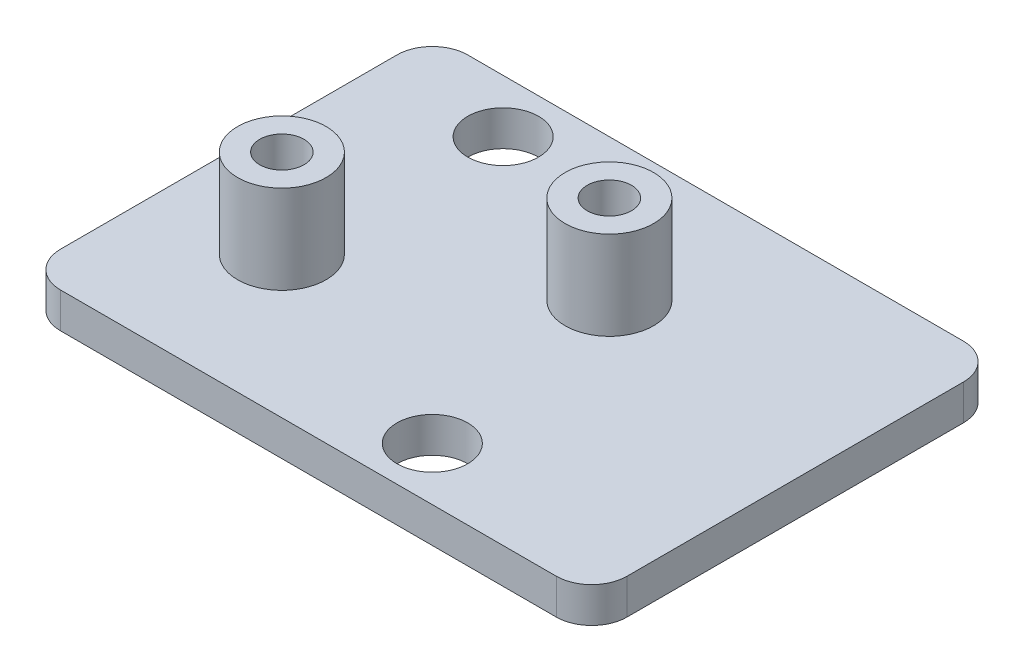
SolidWorks part; units mm, degrees
material "ABS"
ref_plane "Спереди" through (0, 0, 0) normal (0, 0, 1) x (1, 0, 0)
ref_plane "Сверху" through (0, 0, 0) normal (0, 1, 0) x (1, 0, 0)
ref_plane "Справа" through (0, 0, 0) normal (1, 0, 0) x (0, 0, -1)
sketch "Эскиз1" plane through (0, 0, 0) normal (0, 1, 0) x (1, 0, 0)
  line L1 (0, 0) -> (32, 0)
  line L2 (0, 0) -> (0, -23)
  line L3 (0, -23) -> (32, -23)
  line L4 (32, 0) -> (32, -23)
  dimension "D1" = 32
  dimension "D2" = 23
extrude "Бобышка-Вытянуть1" add sketch "Эскиз1" along normal blind 2
sketch "Эскиз4" plane through (0, 2, 0) normal (0, 1, 0) x (1, 0, 0)
  line L0 (0, 0) -> (32, 0) construction
  line L1 (0, -23) -> (32, -23) construction
  line L2 (0, 0) -> (0, -23) construction
  line L3 (32, 0) -> (32, -23) construction
  circle A0 centre (18, -8) radius 2.5
  circle A1 centre (6.5, -15) radius 2.5
  dimension "D1" = 8
  dimension "D2" = 8
  dimension "D3" = 6.5
  dimension "D4" = 14
  dimension "D5" = 5
  dimension "D6" = 5
extrude "Бобышка-Вытянуть2" add sketch "Эскиз4" along normal blind 5
sketch "Эскиз5" plane through (0, 7, 0) normal (0, 1, 0) x (1, 0, 0)
  circle A0 centre (6.5, -15) radius 1.25
  circle A1 centre (18, -8) radius 1.25
  dimension "D1" = 2.5
  dimension "D2" = 2.5
extrude "Вырез-Вытянуть1" cut sketch "Эскиз5" against normal through all
sketch "Эскиз7" plane through (0, 2, 0) normal (0, 1, 0) x (1, 0, 0)
  line L0 (0, 0) -> (32, 0) construction
  line L1 (0, -23) -> (32, -23) construction
  line L2 (32, 0) -> (32, -23) construction
  line L3 (0, 0) -> (0, -23) construction
  circle A0 centre (7, -3) radius 2
  circle A1 centre (20, -20) radius 2
  dimension "D1" = 3
  dimension "D2" = 4
  dimension "D3" = 3
  dimension "D4" = 4
  dimension "D5" = 12
  dimension "D6" = 7
extrude "Вырез-Вытянуть2" cut sketch "Эскиз7" against normal through all
fillet "Скругление1" radius 2 1 edges at (0, 1, 0) type face fillet first side face at (16, 1, 0) second side face at (0, 1, 11.5)
fillet "Скругление2" radius 2 1 edges at (0, 1, 23) type face fillet first side face at (0, 1, 12.5) second side face at (16, 1, 23)
fillet "Скругление3" radius 2 1 edges at (32, 1, 23) type face fillet first side face at (17, 1, 23) second side face at (32, 1, 11.5)
fillet "Скругление4" radius 2 1 edges at (32, 1, 0) type face fillet first side face at (17, 1, 0) second side face at (32, 1, 10.5)
